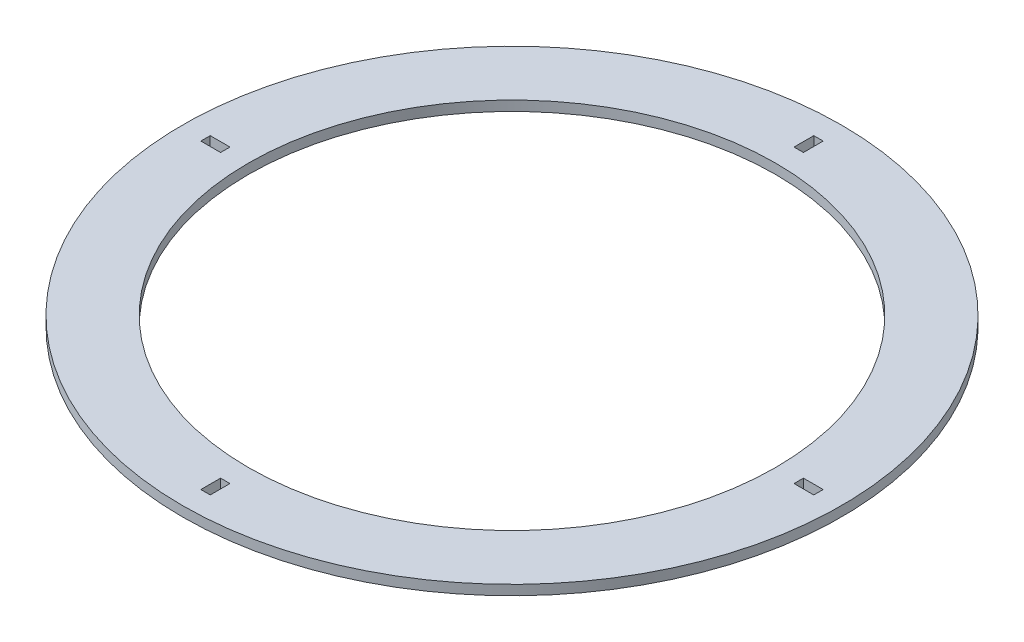
SolidWorks part; units mm, degrees
ref_plane "Front Plane" through (0, 0, 0) normal (0, 0, 1) x (1, 0, 0)
ref_plane "Top Plane" through (0, 0, 0) normal (0, 1, 0) x (1, 0, 0)
ref_plane "Right Plane" through (0, 0, 0) normal (1, 0, 0) x (0, 0, -1)
ref_plane "Base Height Plane" through (0, 0, 0) normal (0, 1, 0) x (1, 0, 0)
sketch "Sketch2" plane through (0, 0, 0) normal (0, 1, 0) x (1, 0, 0)
  line L0 (0, -80) -> (0, -100) construction
  circle A0 centre (0, 0) radius 100
  circle A1 centre (0, 0) radius 80
  point P7 (0, -90)
  dimension "D1" = 200
  dimension "D2" = 20
extrude "Boss-Extrude1" add sketch "Sketch2" along normal blind 3
sketch "Sketch3" plane through (0, 3, 0) normal (0, 1, 0) x (1, 0, 0)
  line L1 (1.425, -93) -> (-1.425, -93)
  line L2 (1.425, -93) -> (1.425, -87)
  line L3 (1.425, -87) -> (-1.425, -87)
  line L4 (-1.425, -93) -> (-1.425, -87)
  line L5 (0, -87) -> (0, -93) construction
  line L6 (1.425, -90) -> (-1.425, -90) construction
  point P0 (0, -90)
  point P4 (0, -92.8018)
  point P5 (0, -93)
  point P6 (0, 0)
  dimension "D2" = 2.85
extrude "Cut-Extrude1" cut sketch "Sketch3" against normal through all
pattern_circular "CirPattern1" count 4 over 360 about axis through (0, 3, 0) along (0, -1, 0) of "Cut-Extrude1"
